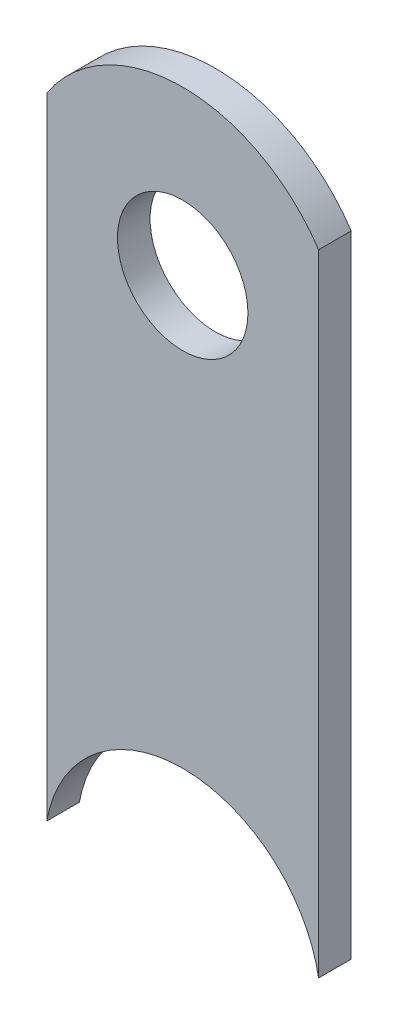
SolidWorks part; units mm, degrees
ref_plane "Front Plane" through (0, 0, 0) normal (0, 0, 1) x (1, 0, 0)
ref_plane "Top Plane" through (0, 0, 0) normal (0, 1, 0) x (1, 0, 0)
ref_plane "Right Plane" through (0, 0, 0) normal (1, 0, 0) x (0, 0, -1)
sketch "Sketch1" plane through (0, 0, 0) normal (0, 0, 1) x (1, 0, 0)
  line L2 (-12.5, 29) -> (-12.5, -29)
  line L4 (12.5, 29) -> (12.5, -29)
  line L5 (-12.5, 29) -> (12.5, -29) construction
  line L6 (-12.5, -29) -> (12.5, 29) construction
  arc A0 (-12.5, 29) -> (12.5, 29) centre (0, 20.7084) cw
  arc A1 (-12.5, -29) -> (12.5, -29) centre (0, -31.245) cw
  circle A2 centre (0, 20.7084) radius 6
  point P0 (0, 0)
  point P9 (0, 0)
  point P10 (0, 0)
  point P11 (0, 35.7084)
  dimension "D1" = 58
  dimension "D3" = 12.7
  dimension "D4" = 12
  dimension "D2" = 25
  dimension "D5" = 58
  dimension "D6" = 15
base flange "Base-Flange1" sketch "Sketch1" thickness 3 reverse thickness direction no parameters "D1"=0.7366
sketch "Bend-Lines1" [suppressed] plane through (0, 0, 0) normal (0, 1, 0) x (1, 0, 0)
sketch "Bounding-Box1" [suppressed] plane through (0, 0, 0) normal (0, 1, 0) x (1, 0, 0)
sheet metal parameters "Sheet-Metal2" thickness 3 parameters "D1"=0.7366
flat pattern "Flat-Pattern2" [suppressed]
sketch "Bend-Lines2" plane through (0, 0, 0) normal (0, 1, 0) x (1, 0, 0)
sketch3d "Bounding-Box2" [suppressed]
  line L0 (12.5, 66.9534, 0) -> (12.5, 2.245, 0) construction
  line L1 (-12.5, 66.9534, 0) -> (-12.5, 2.245, 0) construction
  line L2 (12.5, 66.9534, 0) -> (-12.5, 66.9534, 0) construction
  line L3 (12.5, 2.245, 0) -> (-12.5, 2.245, 0) construction
